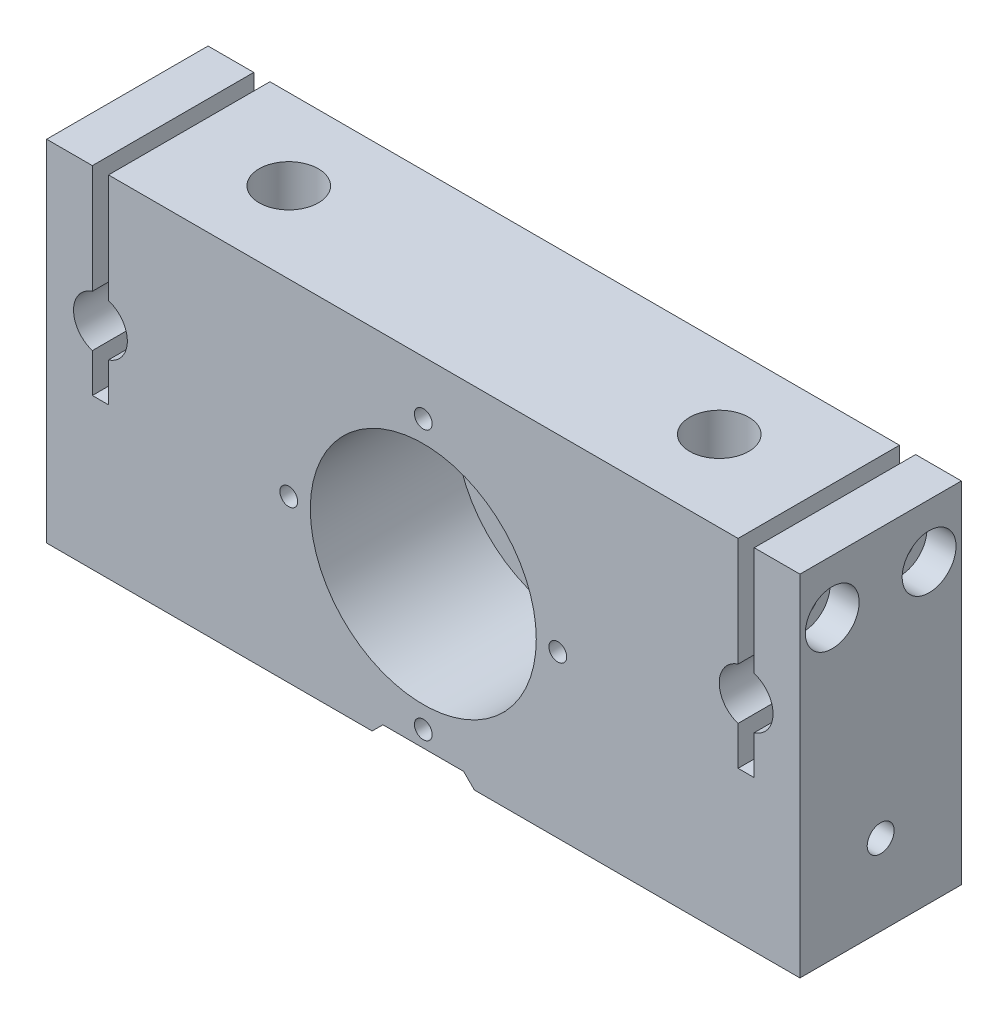
SolidWorks part; units mm, degrees
material "6061 Alloy"
ref_plane "Ön Düzlem" through (0, 0, 0) normal (0, 0, 1) x (1, 0, 0)
ref_plane "Üst Düzlem" through (0, 0, 0) normal (0, 1, 0) x (1, 0, 0)
ref_plane "Sağ Düzlem" through (0, 0, 0) normal (1, 0, 0) x (0, 0, -1)
sketch "Sketch1" plane through (0, 0, 0) normal (0, 0, 1) x (1, 0, 0)
  line L1 (-70, 32.5) -> (70, 32.5)
  line L2 (-70, 32.5) -> (-70, -32.5)
  line L3 (-70, -32.5) -> (70, -32.5)
  line L4 (70, 32.5) -> (70, -32.5)
  line L5 (-70, 32.5) -> (70, -32.5) construction
  line L6 (-70, -32.5) -> (70, 32.5) construction
  point P0 (0, 0)
  dimension "D1" = 65
  dimension "D2" = 140
extrude "Boss-Extrude1" add sketch "Sketch1" along normal blind 30
sketch "Sketch2" plane through (0, 0, 30) normal (0, 0, -1) x (-1, 0, 0)
  line L0 (0, -2.5) -> (0, 32.5) construction
  line L2 (-70, 32.5) -> (70, 32.5) construction
  circle A0 centre (0, -2.5) radius 21
  dimension "D1" = 35
  dimension "D4" = 42
extrude "Cut-Extrude2" cut sketch "Sketch2" along normal blind 27
sketch "Sketch4" plane through (0, 0, 3) normal (0, 0, 1) x (1, 0, 0)
  circle A0 centre (0, -2.5) radius 16.75
  dimension "D1" = 33.5
extrude "Cut-Extrude3" cut sketch "Sketch4" against normal through all
sketch "Sketch5" plane through (0, 0, 0) normal (0, 0, -1) x (-1, 0, 0)
  line L0 (0, -2.5) -> (0, 7.5) construction
  line L1 (-60, 7.5) -> (60, 7.5) construction
  circle A0 centre (-60, 7.5) radius 5
  circle A1 centre (60, 7.5) radius 5
  point P7 (0, 7.5)
  dimension "D3" = 10
  dimension "D1" = 10
  dimension "180" = 120
extrude "Cut-Extrude4" cut sketch "Sketch5" against normal through all
sketch "Sketch6" plane through (0, 0, 0) normal (0, 0, -1) x (-1, 0, 0)
  line L0 (-70, 32.5) -> (70, 32.5) construction
  line L1 (-61.5, 32.5) -> (-58.5, 32.5)
  line L2 (-61.5, 32.5) -> (-61.5, -4.5)
  line L3 (-61.5, -4.5) -> (-58.5, -4.5)
  line L4 (-58.5, 32.5) -> (-58.5, -4.5)
  line L5 (-60, 7.5) -> (-60, 32.5) construction
  line L6 (0, 0) -> (0, 32.5) construction
  line L7 (61.5, -4.5) -> (58.5, -4.5)
  line L8 (58.5, 32.5) -> (58.5, -4.5)
  line L9 (61.5, 32.5) -> (58.5, 32.5)
  line L10 (61.5, 32.5) -> (61.5, -4.5)
  dimension "D1" = 3
  dimension "D2" = 12
extrude "Cut-Extrude5" cut sketch "Sketch6" against normal through all
sketch "Sketch7" plane through (70, 0, 0) normal (1, 0, 0) x (0, 0, -1)
  line L0 (-15, 32.5) -> (-15, 22.5) construction
  line L1 (-30, 32.5) -> (0, 32.5) construction
  line L2 (-24, 22.5) -> (-6, 22.5) construction
  point P7 (-15, 22.5)
  dimension "D1" = 10
  dimension "D2" = 18
hole_wizard "CBORE for M5 Hex Socket Head Cap Screw1" positions "Sketch8" profile "Sketch9" counterbore size "M5" standard "ISO" end condition up to next
sketch "Sketch8" plane through (70, 0, 0) normal (1, 0, 0) x (0, 0, -1)
  point P0 (-6, 22.5)
  point P3 (-24, 22.5)
sketch "Sketch9" plane through (70, 22.5, 6) normal (0, 1, 0) x (0, 0, -1)
  line L0 (0, 0) -> (0, 8.5)
  line L1 (0, 8.5) -> (2.75, 8.5)
  line L3 (2.75, 8.5) -> (2.75, 5.4)
  line L4 (2.75, 5.4) -> (5, 5.4)
  line L5 (5, 5.4) -> (5, 0)
  line L7 (5, 0) -> (0, 0)
  line L11 (0, -6.35) -> (0, 107.95) construction
  dimension "Thru Hole Dia." = 5.5
  dimension "Thru Hole Depth" = 8.5
  dimension "C'Bore Dia." = 10
  dimension "C'Bore Depth" = 5.4
sketch "Sketch10" plane through (58.5, 0, 0) normal (1, 0, 0) x (0, 0, -1)
  point P0 (-24, 22.5)
  point P1 (-6, 22.5)
hole_wizard "Tap Drill for M5 Tap1" positions "Sketch11" profile "Sketch12" hole size "M5" standard "ISO"
sketch "Sketch11" plane through (58.5, 0, 0) normal (1, 0, 0) x (0, 0, -1)
  point P0 (-6, 22.5)
  point P3 (-24, 22.5)
sketch "Sketch12" plane through (58.5, 22.5, 6) normal (0, 1, 0) x (0, 0, -1)
  line L0 (0, 0) -> (0, 13.2618)
  line L1 (0, 13.2618) -> (2.1, 12)
  line L2 (2.1, 12) -> (2.1, 0)
  line L5 (2.1, 0) -> (0, 0)
  line L10 (0, 13.2618) -> (-2.1, 12) construction
  line L11 (0, -6.35) -> (0, 107.95) construction
  dimension "Hole Dia." = 4.2
  dimension "Hole Depth" = 12
  dimension "Drill Angle" = 118
sketch "Sketch13" plane through (70, 0, 0) normal (1, 0, 0) x (0, 0, -1)
  line L0 (-15, -32.5) -> (-15, -17.5) construction
  line L1 (-30, -32.5) -> (0, -32.5) construction
  dimension "D1" = 15
hole_wizard "Tap Drill for M6 Tap1" positions "Sketch14" profile "Sketch15" hole size "M6" standard "ISO"
sketch "Sketch14" plane through (70, 0, 0) normal (1, 0, 0) x (0, 0, -1)
  point P0 (-15, -17.5)
sketch "Sketch15" plane through (70, -17.5, 15) normal (0, 1, 0) x (0, 0, -1)
  line L0 (0, 0) -> (0, 16.5022)
  line L1 (0, 16.5022) -> (2.5, 15)
  line L2 (2.5, 15) -> (2.5, 0)
  line L5 (2.5, 0) -> (0, 0)
  line L10 (0, 16.5022) -> (-2.5, 15) construction
  line L11 (0, -6.35) -> (0, 107.95) construction
  dimension "Hole Dia." = 5
  dimension "Hole Depth" = 15
  dimension "Drill Angle" = 118
mirror "Mirror1" about plane through (0, 0, 0) normal (1, 0, 0) of "Tap Drill for M6 Tap1", "CBORE for M5 Hex Socket Head Cap Screw1", "Tap Drill for M5 Tap1"
sketch "Sketch22" plane through (0, 32.5, 0) normal (0, 1, 0) x (1, 0, 0)
  line L0 (58.5, -15) -> (40, -15) construction
  line L1 (58.5, -30) -> (58.5, 0) construction
  line L2 (40, -15) -> (-40, -15) construction
  line L3 (-40, -15) -> (-58.5, -15) construction
  line L4 (-58.5, -30) -> (-58.5, 0) construction
  dimension "D1" = 80
hole_wizard "CBORE for M6 Hex Socket Head Cap Screw3" positions "Sketch23" profile "Sketch24" counterbore size "M6" standard "ISO" end condition through all
sketch "Sketch23" plane through (0, 32.5, 0) normal (0, 1, 0) x (1, 0, 0)
  point P0 (40, -15)
  point P3 (-40, -15)
sketch "Sketch24" plane through (40, 32.5, 15) normal (1, 0, 0) x (0, 0, 1)
  line L0 (0, 0) -> (0, 65)
  line L1 (0, 65) -> (3.3, 65)
  line L3 (3.3, 65) -> (3.3, 61.4)
  line L4 (3.3, 61.4) -> (5.5, 61.4)
  line L5 (5.5, 61.4) -> (5.5, 0)
  line L7 (5.5, 0) -> (0, 0)
  line L11 (0, -6.35) -> (0, 107.95) construction
  dimension "Thru Hole Dia." = 6.6
  dimension "Thru Hole Depth" = 65
  dimension "C'Bore Dia." = 11
  dimension "C'Bore Depth" = 61.4
sketch "Sketch25" plane through (0, 0, 30) normal (0, 0, 1) x (1, 0, 0)
  line L0 (0, -2.5) -> (0, 22.5) construction
  dimension "D1" = 25
hole_wizard "Tap Drill for M4 Tap1" positions "Sketch26" profile "Sketch28" hole size "M4" standard "ISO"
sketch "Sketch26" plane through (0, 0, 30) normal (0, 0, 1) x (1, 0, 0)
  point P0 (0, 22.5)
sketch "Sketch28" plane through (0, 22.5, 30) normal (1, 0, 0) x (0, -1, 0)
  line L0 (0, 0) -> (0, 8.9914)
  line L1 (0, 8.9914) -> (1.65, 8)
  line L2 (1.65, 8) -> (1.65, 0)
  line L5 (1.65, 0) -> (0, 0)
  line L10 (0, 8.9914) -> (-1.65, 8) construction
  line L11 (0, -6.35) -> (0, 107.95) construction
  dimension "Hole Dia." = 3.3
  dimension "Hole Depth" = 8
  dimension "Drill Angle" = 118
pattern_circular "CirPattern1" count 4 over 360 about axis through (0, -2.5, 3) along (0, 0, 1) of "Tap Drill for M4 Tap1" reverse direction yes
sketch "Sketch29" plane through (0, 0, 30) normal (0, 0, 1) x (1, 0, 0)
  line L0 (-70, -32.5) -> (70, -32.5) construction
  line L2 (-17.5, -30.5) -> (17.5, -30.5)
  line L3 (-17.5, -30.5) -> (-17.5, -32.5)
  line L4 (-17.5, -32.5) -> (17.5, -32.5)
  line L5 (17.5, -30.5) -> (17.5, -32.5)
  point P0 (0, -32.5)
  dimension "D1" = 2
  dimension "D2" = 35
extrude "Cut-Extrude6" cut sketch "Sketch29" against normal through all
chamfer "Chamfer2" distance 10 angle 45 2 edges at (-17.5, -30.5, 15) (17.5, -30.5, 15)
